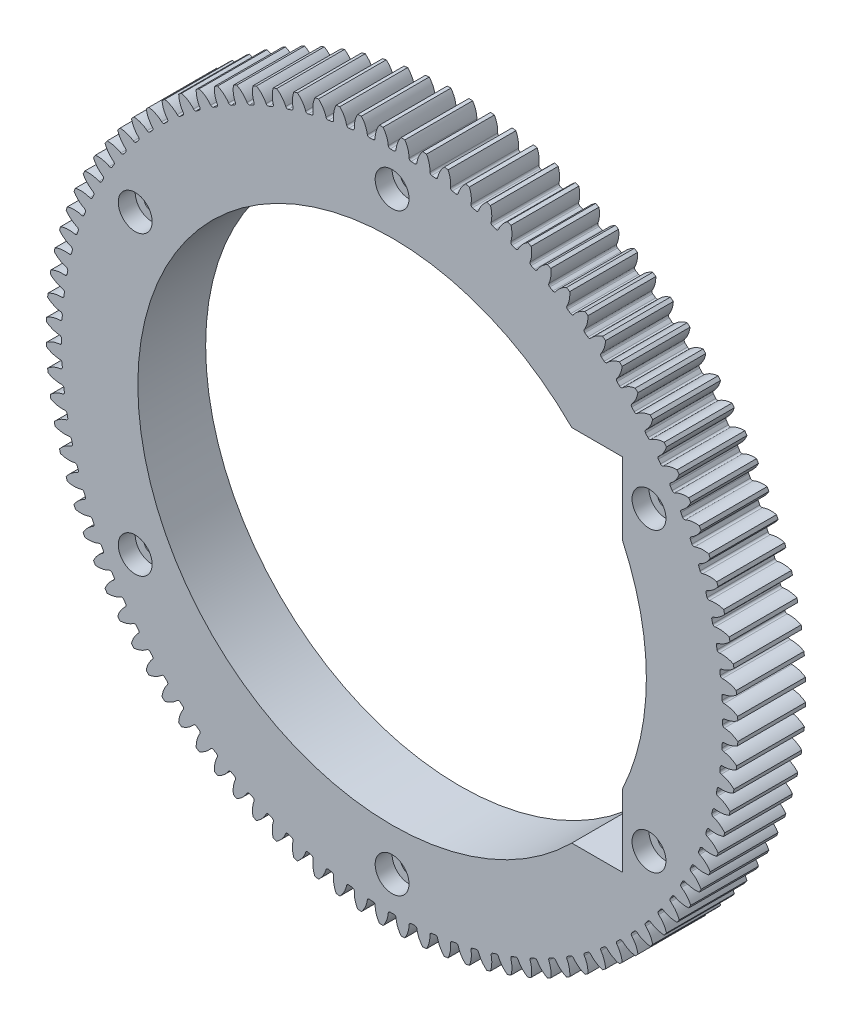
SolidWorks part; units mm, degrees
ref_plane "Front Plane" through (0, 0, 0) normal (0, 0, 1) x (1, 0, 0)
ref_plane "Top Plane" through (0, 0, 0) normal (0, 1, 0) x (1, 0, 0)
ref_plane "Right Plane" through (0, 0, 0) normal (1, 0, 0) x (0, 0, -1)
sketch "Sketch2" plane through (0, 0, 0) normal (0, 0, 1) x (1, 0, 0)
  circle A0 centre (0, 0) radius 100 construction
  circle A1 centre (0, 0) radius 102
  dimension "D1" = 200
  dimension "D2" = 204
extrude "Boss-Extrude1" add sketch "Sketch2" along normal mid plane 20 contours A1
sketch "Sketch3" plane through (0, 0, 0) normal (0, 0, 1) x (1, 0, 0)
  line L0 (0, 102) -> (0, 0) construction
  line L1 (0, 0) -> (6.4046, 101.7987) construction
  line L2 (0, 0) -> (3.2039, 101.9497) construction
  line L3 (-1.1162, 97.4936) -> (0, 0) construction
  line L4 (-1.5707, 99.9877) -> (1.5707, 99.9877) construction
  line L5 (1.5707, 99.9877) -> (4.7106, 99.889) construction
  line L6 (-2.2938, 101.9742) -> (0, 95.6721) construction
  circle A0 centre (0, 0) radius 98 construction
  arc A1 (1.1162, 97.4936) -> (-1.1162, 97.4936) centre (0, 0) ccw
  circle A2 centre (0, 0) radius 102 construction
  circle A3 centre (0, 0) radius 100 construction
  arc A4 (-2.6485, 101.9656) -> (-1.1162, 97.4936) centre (-8.6604, 97.4072) cw
  arc A5 (2.6485, 101.9656) -> (1.1162, 97.4936) centre (8.6604, 97.4072) ccw
  arc A6 (2.6485, 101.9656) -> (-2.6485, 101.9656) centre (0, 0) ccw
  dimension "D4" = 200
  dimension "D1" = 3.6
  dimension "D2" = 4
  dimension "D3" = 4.5
  dimension "D5" = 20
extrude "Cut-Extrude1" cut sketch "Sketch3" against normal through all both and the other way through all
fillet "Fillet1" radius 0.6 2 edges at (1.1162, 97.4936, 0) (-1.1162, 97.4936, 0)
ref_axis "Axis1" through (0, 0, -11) along (0, 0, 1)
pattern_circular "CirPattern1" count 100 over 360 about axis through (0, 0, -11) along (0, 0, 1) of "Cut-Extrude1", "Fillet1"
sketch "Sketch4" plane through (0, 0, -10) normal (0, 0, -1) x (-1, 0, 0)
  circle A0 centre (0, 0) radius 5
  dimension "D1" = 10
extrude "Cut-Extrude3" cut sketch "Sketch4" against normal blind 10
sketch "Sketch5" plane through (0, 0, 10) normal (0, 0, 1) x (1, 0, 0)
  circle A0 centre (0, 0) radius 75
  circle A1 centre (0, 0) radius 87.5 construction
  circle A2 centre (0, 87.5) radius 2.5
  circle A3 centre (75.7772, 43.75) radius 2.5
  circle A4 centre (75.7772, -43.75) radius 2.5
  circle A5 centre (0, -87.5) radius 2.5
  circle A6 centre (-75.7772, -43.75) radius 2.5
  circle A7 centre (-75.7772, 43.75) radius 2.5
  point P18 (0, 0)
  dimension "D1" = 5
  dimension "D2" = 175
  dimension "D3" = 150
  dimension "D4" = 6
extrude "Cut-Extrude4" cut sketch "Sketch5" against normal through all
sketch "Sketch6" plane through (0, 0, 10) normal (0, 0, 1) x (1, 0, 0)
  circle A0 centre (0, 87.5) radius 5
  circle A1 centre (75.7772, 43.75) radius 5
  circle A2 centre (75.7772, -43.75) radius 5
  circle A3 centre (0, -87.5) radius 5
  circle A4 centre (-75.7772, -43.75) radius 5
  circle A5 centre (-75.7772, 43.75) radius 5
  point P16 (0, 0)
  dimension "D1" = 10
  dimension "D2" = 6
extrude "Cut-Extrude5" cut sketch "Sketch6" against normal blind 5
sketch "Sketch7" plane through (0, 0, 10) normal (0, 0, 1) x (1, 0, 0)
  line L1 (-53, 67.5) -> (53, 67.5) construction
  line L2 (-53, 67.5) -> (-53, -67.5) construction
  line L3 (-53, -67.5) -> (53, -67.5) construction
  line L4 (53, 67.5) -> (53, -67.5) construction
  line L5 (-53, 67.5) -> (53, -67.5) construction
  line L6 (-53, -67.5) -> (53, 67.5) construction
  line L7 (53, 53.066) -> (68, 53.066)
  line L8 (53, 53.066) -> (53, -53.066)
  line L9 (53, -53.066) -> (68, -53.066)
  line L10 (68, 53.066) -> (68, -53.066)
  circle A0 centre (0, 0) radius 75 construction
  point P0 (0, 0)
  dimension "D3" = 150
  dimension "D1" = 106
  dimension "D2" = 135
  dimension "D4" = 15
extrude "Cut-Extrude6" cut sketch "Sketch7" against normal blind 20
equation "\"Module\"= 2"
equation "\"Number of teeth\"= 100"
equation "\"pressure angle\"= 20"
equation "\"D1@Sketch2\"=\"Module\"*\"Number of teeth\""
equation "\"D2@Sketch2\"=(\"Number of teeth\"+2) *\"Module\""
equation "\"D1@Sketch3\"=360 /\"Number of teeth\""
equation "\"D2@Sketch3\"=\"Module\"*2"
equation "\"D3@Sketch3\"=\"Module\" *if( \"Module\"=> 1.25,2.25,2.4)"
equation "\"D5@Sketch3\"=\"pressure angle\""
equation "\"D4@Sketch3\"=\"Module\"*\"Number of teeth\""
equation "\"D1@CirPattern1\"=\"Number of teeth\""
equation "\"D1@Fillet1\"=0.3 *\"Module\""
